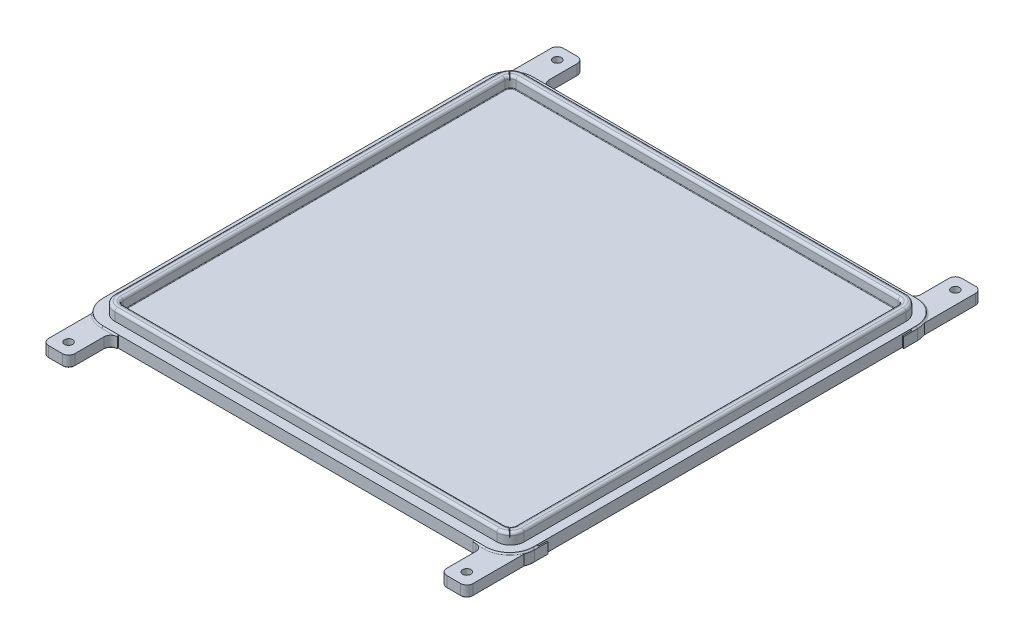
SolidWorks part; units mm, degrees
ref_plane "Front Plane" through (0, 0, 0) normal (0, 0, 1) x (1, 0, 0)
ref_plane "Top Plane" through (0, 0, 0) normal (0, 1, 0) x (1, 0, 0)
ref_plane "Right Plane" through (0, 0, 0) normal (1, 0, 0) x (0, 0, -1)
sketch "Sketch1" plane through (0, 0, 0) normal (0, 1, 0) x (1, 0, 0)
  line L8 (-70, -78.7) -> (70, -78.7)
  line L9 (78.7, -70) -> (78.7, 70)
  line L10 (70, 78.7) -> (-70, 78.7)
  line L11 (-78.7, 70) -> (-78.7, -70)
  line L12 (-70, 70) -> (70, -70) construction
  line L13 (70, -70) -> (70, 70) construction
  line L14 (70, 70) -> (-70, -70) construction
  arc A8 (-78.7, -70) -> (-70, -78.7) centre (-70, -70) ccw
  arc A9 (70, -78.7) -> (78.7, -70) centre (70, -70) ccw
  arc A10 (78.7, 70) -> (70, 78.7) centre (70, 70) ccw
  arc A11 (-70, 78.7) -> (-78.7, 70) centre (-70, 70) ccw
  point P13 (0, 0)
  dimension "D1" = 140
  dimension "D2" = 140
extrude "Boss-Extrude1" add sketch "Sketch1" along normal blind 4.5
sketch "Sketch2" plane through (0, 4.5, 0) normal (0, 1, 0) x (1, 0, 0)
  line L0 (-74.1708, 69.5068) -> (-74.1708, -70.1199)
  line L9 (-69.1708, -75.1199) -> (70.4559, -75.1199)
  line L12 (75.4559, -70.1199) -> (75.4559, 69.5068)
  line L15 (70.4559, 74.5068) -> (-69.1708, 74.5068)
  arc A11 (-74.1708, -70.1199) -> (-69.1708, -75.1199) centre (-69.1708, -70.1199) ccw
  arc A12 (75.4559, -70.1199) -> (70.4559, -75.1199) centre (70.4559, -70.1199) cw
  arc A13 (75.4559, 69.5068) -> (70.4559, 74.5068) centre (70.4559, 69.5068) ccw
  arc A14 (-74.1708, 69.5068) -> (-69.1708, 74.5068) centre (-69.1708, 69.5068) cw
  point P0 (0, 0)
  dimension "D1" = 5
extrude "Extrude-Thin1" add sketch "Sketch2" along normal blind 4 thin thin type one direction reverse wall 3
fillet "Fillet1" radius 1 16 edges at (-71.1708, 8.5, 0.3065) (0.6426, 8.5, 72.1199) (72.4559, 8.5, 0.3065) (0.6426, 8.5, -71.5068) (0.6426, 8.5, -74.5068) (75.4559, 8.5, 0.3065) (0.6426, 8.5, 75.1199) (-74.1708, 8.5, 0.3065) (71.8701, 8.5, 71.5341) (71.8701, 8.5, -70.921) (-70.585, 8.5, -70.921) (-70.585, 8.5, 71.5341) (-72.7063, 8.5, -73.0423) (73.9915, 8.5, -73.0423) (73.9915, 8.5, 73.6554) (-72.7063, 8.5, 73.6554)
sketch "Sketch3" plane through (0, 8.5, 0) normal (0, 1, 0) x (1, 0, 0)
  line L0 (-75, 70) -> (-75, 75) construction
  line L1 (-70, 75) -> (-75, 75) construction
  line L2 (-75.0707, 74.9293) -> (-74.9293, 75.0707) construction
  line L3 (-75.0707, 74.9293) -> (78.5176, -78.659)
  line L4 (78.5176, -78.659) -> (78.659, -78.5176)
  line L5 (78.659, -78.5176) -> (-74.9293, 75.0707)
  line L6 (-74.9293, 75.0707) -> (-75.0707, 74.9293)
  point P10 (-75, 75)
extrude "Cut-Extrude1" cut sketch "Sketch3" against normal blind 3.8 draft 2.5
fillet "Fillet2" radius 0.2 8 edges at (-71.1708, 4.5, 0.3065) (-70.585, 4.5, -70.921) (0.6426, 4.5, -71.5068) (71.8701, 4.5, -70.921) (72.4559, 4.5, 0.3065) (71.8701, 4.5, 71.5341) (0.6426, 4.5, 72.1199) (-70.585, 4.5, 71.5341)
sketch "Sketch4" plane through (0, 0, 0) normal (0, -1, 0) x (1, 0, 0)
  line L63 (-66.7883, -91.5032) -> (-66.7883, -78.3901)
  line L64 (-66.7883, -78.3901) -> (-64.3539, -78.3901)
  line L65 (-64.3539, -78.3901) -> (-64.3539, -77.9901)
  line L66 (-64.3539, -77.9901) -> (-67.6539, -77.9901)
  line L67 (-67.6539, -77.9901) -> (-67.6539, -76.1401)
  line L68 (-67.6539, -76.1401) -> (-64.3539, -76.1401)
  line L69 (-64.3539, -76.1401) -> (65.9461, -76.1401)
  line L70 (65.9461, -76.1401) -> (68.9461, -76.1401)
  line L71 (68.9461, -76.1401) -> (68.9461, -77.9901)
  line L72 (68.9461, -77.9901) -> (65.9461, -77.9901)
  line L73 (65.9461, -77.9901) -> (65.6461, -77.9901)
  line L74 (65.6461, -77.9901) -> (65.6461, -78.3901)
  line L75 (65.6461, -78.3901) -> (69.1461, -78.3901)
  line L76 (69.1461, -78.3901) -> (69.1461, -91.5032)
  line L77 (71.4461, -93.8032) -> (76.4678, -93.8032)
  line L78 (78.7678, -91.5032) -> (78.7678, -72.8087)
  line L79 (79.3459, -69.6901) -> (79.3459, -64.6901)
  line L80 (79.3459, -64.6901) -> (78.9459, -64.6901)
  line L81 (78.9459, -64.6901) -> (78.9459, -64.9901)
  line L82 (78.9459, -64.9901) -> (78.9459, -67.9901)
  line L83 (78.9459, -67.9901) -> (77.0959, -67.9901)
  line L84 (77.0959, -67.9901) -> (77.0959, -64.9901)
  line L85 (77.0959, -64.9901) -> (77.0959, 65.6099)
  line L86 (77.0959, 65.6099) -> (77.0959, 68.6099)
  line L87 (77.0959, 68.6099) -> (78.9459, 68.6099)
  line L88 (78.9459, 68.6099) -> (78.9459, 65.6099)
  line L89 (78.9459, 65.6099) -> (78.9459, 65.3099)
  line L90 (78.9459, 65.3099) -> (79.3459, 65.3099)
  line L91 (79.3459, 65.3099) -> (79.3459, 70.3099)
  line L92 (78.7678, 73.4284) -> (78.7678, 92.1229)
  line L93 (76.4678, 94.4229) -> (71.4461, 94.4229)
  line L94 (69.1461, 92.1229) -> (69.1461, 79.0099)
  line L95 (69.1461, 79.0099) -> (65.6461, 79.0099)
  line L96 (65.6461, 79.0099) -> (65.6461, 78.6099)
  line L97 (65.6461, 78.6099) -> (65.9461, 78.6099)
  line L98 (65.9461, 78.6099) -> (68.9461, 78.6099)
  line L99 (68.9461, 78.6099) -> (68.9461, 76.7599)
  line L100 (68.9461, 76.7599) -> (65.9461, 76.7599)
  line L101 (65.9461, 76.7599) -> (-64.6539, 76.7599)
  line L102 (-64.6539, 76.7599) -> (-67.6539, 76.7599)
  line L103 (-67.6539, 76.7599) -> (-67.6539, 78.6099)
  line L104 (-67.6539, 78.6099) -> (-64.6539, 78.6099)
  line L105 (-64.6539, 78.6099) -> (-64.3539, 78.6099)
  line L106 (-64.3539, 78.6099) -> (-64.3539, 79.0099)
  line L107 (-64.3539, 79.0099) -> (-66.7883, 79.0099)
  line L108 (-66.7883, 79.0099) -> (-66.7883, 92.1229)
  line L109 (-69.0883, 94.4229) -> (-74.1099, 94.4229)
  line L110 (-76.4099, 92.1229) -> (-76.4099, 75.3996)
  line L111 (-78.0541, 70.3099) -> (-78.0541, 65.3099)
  line L112 (-78.0541, 65.3099) -> (-77.6541, 65.3099)
  line L113 (-77.6541, 65.3099) -> (-77.6541, 65.6099)
  line L114 (-77.6541, 65.6099) -> (-77.6541, 68.6099)
  line L115 (-77.6541, 68.6099) -> (-75.8041, 68.6099)
  line L116 (-75.8041, 68.6099) -> (-75.8041, 65.6099)
  line L117 (-75.8041, 65.6099) -> (-75.8041, -64.9901)
  line L118 (-75.8041, -64.9901) -> (-75.8041, -67.9901)
  line L119 (-75.8041, -67.9901) -> (-77.6541, -67.9901)
  line L120 (-77.6541, -67.9901) -> (-77.6541, -64.9901)
  line L121 (-77.6541, -64.9901) -> (-77.6541, -64.8901)
  line L122 (-77.6541, -64.8901) -> (-78.0541, -64.8901)
  line L123 (-78.0541, -64.8901) -> (-78.0541, -69.6901)
  line L124 (-76.4099, -74.7799) -> (-76.4099, -91.5032)
  line L125 (-74.1099, -93.8032) -> (-69.0883, -93.8032)
  line L126 (-66.7883, -91.5032) -> (-66.7883, -78.3901)
  line L127 (-66.7883, -78.3901) -> (-64.3539, -78.3901)
  line L128 (-64.3539, -78.3901) -> (-64.3539, -77.9901)
  line L129 (-64.3539, -77.9901) -> (-67.6539, -77.9901)
  line L130 (-67.6539, -77.9901) -> (-67.6539, -76.1401)
  line L131 (-67.6539, -76.1401) -> (-64.3539, -76.1401)
  line L132 (-64.3539, -76.1401) -> (65.9461, -76.1401)
  line L133 (65.9461, -76.1401) -> (68.9461, -76.1401)
  line L134 (68.9461, -76.1401) -> (68.9461, -77.9901)
  line L135 (68.9461, -77.9901) -> (65.9461, -77.9901)
  line L136 (65.9461, -77.9901) -> (65.6461, -77.9901)
  line L137 (65.6461, -77.9901) -> (65.6461, -78.3901)
  line L138 (65.6461, -78.3901) -> (69.1461, -78.3901)
  line L139 (69.1461, -78.3901) -> (69.1461, -91.5032)
  line L140 (71.4461, -93.8032) -> (76.4678, -93.8032)
  line L141 (78.7678, -91.5032) -> (78.7678, -72.8087)
  line L142 (79.3459, -69.6901) -> (79.3459, -64.6901)
  line L143 (79.3459, -64.6901) -> (78.9459, -64.6901)
  line L144 (78.9459, -64.6901) -> (78.9459, -64.9901)
  line L145 (78.9459, -64.9901) -> (78.9459, -67.9901)
  line L146 (78.9459, -67.9901) -> (77.0959, -67.9901)
  line L147 (77.0959, -67.9901) -> (77.0959, -64.9901)
  line L148 (77.0959, -64.9901) -> (77.0959, 65.6099)
  line L149 (77.0959, 65.6099) -> (77.0959, 68.6099)
  line L150 (77.0959, 68.6099) -> (78.9459, 68.6099)
  line L151 (78.9459, 68.6099) -> (78.9459, 65.6099)
  line L152 (78.9459, 65.6099) -> (78.9459, 65.3099)
  line L153 (78.9459, 65.3099) -> (79.3459, 65.3099)
  line L154 (79.3459, 65.3099) -> (79.3459, 70.3099)
  line L155 (78.7678, 73.4284) -> (78.7678, 92.1229)
  line L156 (76.4678, 94.4229) -> (71.4461, 94.4229)
  line L157 (69.1461, 92.1229) -> (69.1461, 79.0099)
  line L158 (69.1461, 79.0099) -> (65.6461, 79.0099)
  line L159 (65.6461, 79.0099) -> (65.6461, 78.6099)
  line L160 (65.6461, 78.6099) -> (65.9461, 78.6099)
  line L161 (65.9461, 78.6099) -> (68.9461, 78.6099)
  line L162 (68.9461, 78.6099) -> (68.9461, 76.7599)
  line L163 (68.9461, 76.7599) -> (65.9461, 76.7599)
  line L164 (65.9461, 76.7599) -> (-64.6539, 76.7599)
  line L165 (-64.6539, 76.7599) -> (-67.6539, 76.7599)
  line L166 (-67.6539, 76.7599) -> (-67.6539, 78.6099)
  line L167 (-67.6539, 78.6099) -> (-64.6539, 78.6099)
  line L168 (-64.6539, 78.6099) -> (-64.3539, 78.6099)
  line L169 (-64.3539, 78.6099) -> (-64.3539, 79.0099)
  line L170 (-64.3539, 79.0099) -> (-66.7883, 79.0099)
  line L171 (-66.7883, 79.0099) -> (-66.7883, 92.1229)
  line L172 (-69.0883, 94.4229) -> (-74.1099, 94.4229)
  line L173 (-76.4099, 92.1229) -> (-76.4099, 75.3996)
  line L174 (-78.0541, 70.3099) -> (-78.0541, 65.3099)
  line L175 (-78.0541, 65.3099) -> (-77.6541, 65.3099)
  line L176 (-77.6541, 65.3099) -> (-77.6541, 65.6099)
  line L177 (-77.6541, 65.6099) -> (-77.6541, 68.6099)
  line L178 (-77.6541, 68.6099) -> (-75.8041, 68.6099)
  line L179 (-75.8041, 68.6099) -> (-75.8041, 65.6099)
  line L180 (-75.8041, 65.6099) -> (-75.8041, -64.9901)
  line L181 (-75.8041, -64.9901) -> (-75.8041, -67.9901)
  line L182 (-75.8041, -67.9901) -> (-77.6541, -67.9901)
  line L183 (-77.6541, -67.9901) -> (-77.6541, -64.9901)
  line L184 (-77.6541, -64.9901) -> (-77.6541, -64.8901)
  line L185 (-77.6541, -64.8901) -> (-78.0541, -64.8901)
  line L186 (-78.0541, -64.8901) -> (-78.0541, -69.6901)
  line L187 (-76.4099, -74.7799) -> (-76.4099, -91.5032)
  line L188 (-74.1099, -93.8032) -> (-69.0883, -93.8032)
  arc A12 (69.1461, -91.5032) -> (71.4461, -93.8032) centre (71.4461, -91.5032) ccw
  arc A13 (76.4678, -93.8032) -> (78.7678, -91.5032) centre (76.4678, -91.5032) ccw
  arc A14 (78.7678, -72.8087) -> (79.3459, -69.6901) centre (70.6459, -69.6901) ccw
  arc A15 (79.3459, 70.3099) -> (78.7678, 73.4284) centre (70.6459, 70.3099) ccw
  arc A16 (78.7678, 92.1229) -> (76.4678, 94.4229) centre (76.4678, 92.1229) ccw
  arc A17 (71.4461, 94.4229) -> (69.1461, 92.1229) centre (71.4461, 92.1229) ccw
  arc A18 (-66.7883, 92.1229) -> (-69.0883, 94.4229) centre (-69.0883, 92.1229) ccw
  arc A19 (-74.1099, 94.4229) -> (-76.4099, 92.1229) centre (-74.1099, 92.1229) ccw
  arc A20 (-76.4099, 75.3996) -> (-78.0541, 70.3099) centre (-69.3541, 70.3099) ccw
  arc A21 (-78.0541, -69.6901) -> (-76.4099, -74.7799) centre (-69.3541, -69.6901) ccw
  arc A22 (-76.4099, -91.5032) -> (-74.1099, -93.8032) centre (-74.1099, -91.5032) ccw
  arc A23 (-69.0883, -93.8032) -> (-66.7883, -91.5032) centre (-69.0883, -91.5032) ccw
  arc A24 (69.1461, -91.5032) -> (71.4461, -93.8032) centre (71.4461, -91.5032) ccw
  arc A25 (76.4678, -93.8032) -> (78.7678, -91.5032) centre (76.4678, -91.5032) ccw
  arc A26 (78.7678, -72.8087) -> (79.3459, -69.6901) centre (70.6459, -69.6901) ccw
  arc A27 (79.3459, 70.3099) -> (78.7678, 73.4284) centre (70.6459, 70.3099) ccw
  arc A28 (78.7678, 92.1229) -> (76.4678, 94.4229) centre (76.4678, 92.1229) ccw
  arc A29 (71.4461, 94.4229) -> (69.1461, 92.1229) centre (71.4461, 92.1229) ccw
  arc A30 (-66.7883, 92.1229) -> (-69.0883, 94.4229) centre (-69.0883, 92.1229) ccw
  arc A31 (-74.1099, 94.4229) -> (-76.4099, 92.1229) centre (-74.1099, 92.1229) ccw
  arc A32 (-76.4099, 75.3996) -> (-78.0541, 70.3099) centre (-69.3541, 70.3099) ccw
  arc A33 (-78.0541, -69.6901) -> (-76.4099, -74.7799) centre (-69.3541, -69.6901) ccw
  arc A34 (-76.4099, -91.5032) -> (-74.1099, -93.8032) centre (-74.1099, -91.5032) ccw
  arc A35 (-69.0883, -93.8032) -> (-66.7883, -91.5032) centre (-69.0883, -91.5032) ccw
  dimension "D1" = 0
extrude "Boss-Extrude2" add sketch "Sketch4" against normal blind 4
fillet "Fillet4" radius 0.5 1 edges at (-67.1769, 4, 78.7) type face fillet first side face at (-69.8442, 4, 85.1133) second side face at (0.3231, 3.125, 78.7) second side face at (0, 4.5, 0)
fillet "Fillet6" radius 0.5 1 edges at (67.8231, 4, 78.7) type face fillet first side face at (74.7309, 4, 78.1914) second side face at (23.7641, 2.8333, 78.7) second side face at (-13.981, 4.5, 15.3669)
fillet "Fillet7" radius 0.5 1 edges at (69.5731, 4, -78.7) type face fillet first side face at (76.1285, 4, -77.5887) second side face at (0.5895, 3.125, -78.7) second side face at (0.378, 4.5, 25.0816)
fillet "Fillet8" radius 0.5 1 edges at (-68.3941, 4, -78.7) type face fillet first side face at (-71.4129, 4, -86.503) second side face at (-22.5474, 2.8333, -78.7) second side face at (10.8844, 4.5, 11.0206)
fillet "Fillet9" radius 2.5 6 edges at (-76.4099, 2.25, 75.8824) (-66.7883, 2.0188, 79.0099) (69.1461, 2.0188, 79.0099) (69.1461, 2.25, -78.7) (-66.7883, 2.25, -78.7) (-76.4099, 2.25, -75.8824)
chamfer "Chamfer1" distance 0.2 angle 45 45 edges at (0.6461, 0, 78.7) (78.7, 0, 0.3099) (1.1789, 0, -78.7) (-78.2433, 0, -72.7818) (-78.7, 0, 0) (-78.2433, 0, 72.7818) (-66.056, 0, -79.4322) (-66.7883, 0, -86.3516) (-67.4619, 0, -93.1295) (-71.5991, 0, -93.8032) (-75.7362, 0, -93.1295) (-76.4099, 0, -84.1447) (-76.5411, 0, -75.9869) (-76.5411, 0, 75.9869) (-76.4099, 0, 84.4546) (-75.7362, 0, 93.7493) (-71.5991, 0, 94.4229) (-67.4619, 0, 93.7493) (-66.7883, 0, 86.816) (-66.0791, 0, 79.7646) (-64.3539, 0, 78.8549) (65.6461, 0, 78.8549) (66.1461, 0, 79.0099) (68.4139, 0, 79.7421) (69.1461, 0, 86.8164) (69.8198, 0, 93.7493) (73.957, 0, 94.4229) (78.0941, 0, 93.7493) (78.7678, 0, 82.7757) (79.2002, 0, 71.8957) (79.3459, 0, 67.8099) (79.1459, 0, 65.3099) (78.9459, 0, 66.9599) (78.823, 0, 68.6099) (78.823, 0, -67.9901) (78.9459, 0, -66.3401) (79.1459, 0, -64.6901) (79.3459, 0, -67.1901) (79.2002, 0, -71.276) (78.7678, 0, -82.1559) (78.0941, 0, -93.1295) (73.957, 0, -93.8032) (69.8198, 0, -93.1295) (69.1461, 0, -86.3516) (68.4139, 0, -79.4322)
sketch "Sketch5" plane through (0, 0, 0) normal (0, -1, 0) x (1, 0, 0)
  circle A0 centre (-71.5991, -89.0032) radius 1.5 construction
  circle A1 centre (73.957, -89.0032) radius 1.5 construction
  circle A2 centre (73.957, 89.6229) radius 1.5 construction
  circle A3 centre (-71.5991, 89.6229) radius 1.5 construction
  circle A4 centre (-71.5991, -89.0032) radius 1.5
  circle A5 centre (73.957, -89.0032) radius 1.5
  circle A6 centre (73.957, 89.6229) radius 1.5
  circle A7 centre (-71.5991, 89.6229) radius 1.5
extrude "Cut-Extrude2" cut sketch "Sketch5" against normal blind 4
sketch "Sketch6" plane through (78.7, 0, 0) normal (1, 0, 0) x (0, 0, -1)
  line L0 (-4.2884, 0) -> (4.2884, 0) construction
  line L2 (68.1901, 0) -> (-68.8099, 0) construction
  point P6 (0, 0)
